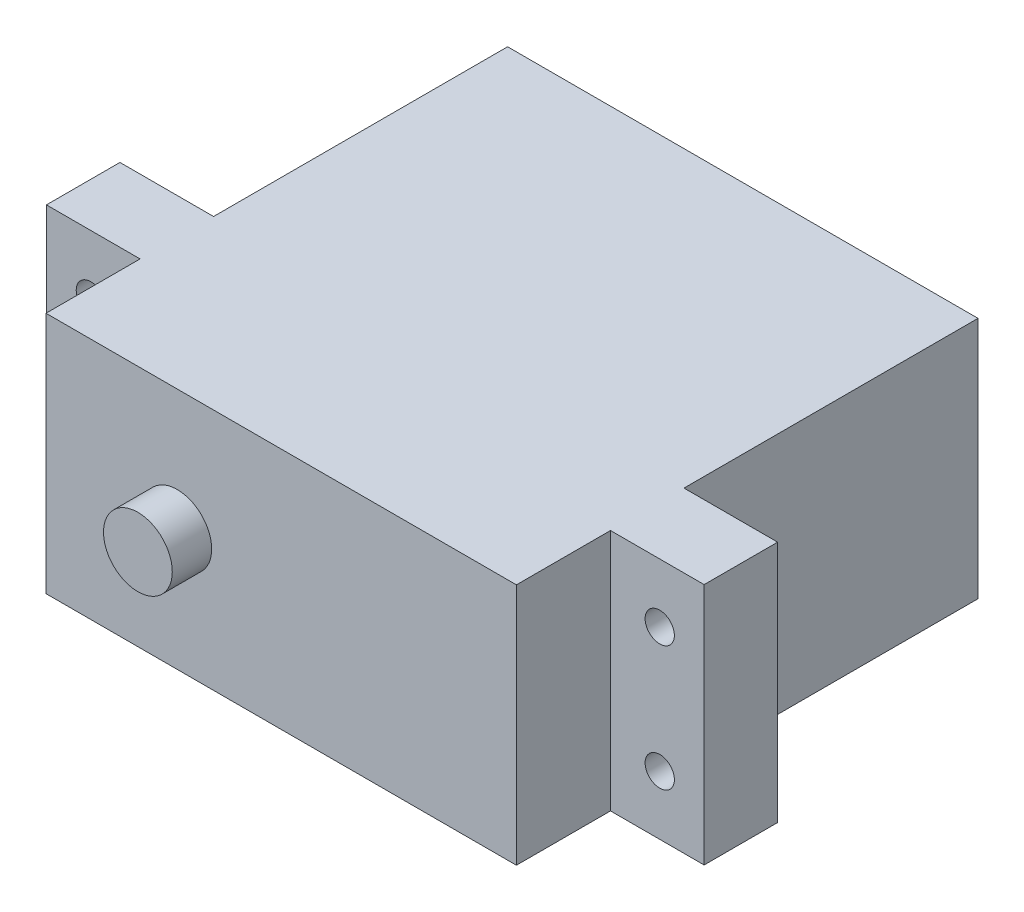
SolidWorks part; units mm, degrees
ref_plane "Front Plane" through (0, 0, 0) normal (0, 0, 1) x (1, 0, 0)
ref_plane "Top Plane" through (0, 0, 0) normal (0, 1, 0) x (1, 0, 0)
ref_plane "Right Plane" through (0, 0, 0) normal (1, 0, 0) x (0, 0, -1)
sketch "Sketch1" plane through (0, 0, 0) normal (0, 0, 1) x (1, 0, 0)
  line L0 (-28.4099, -10.4902) -> (28.4099, -10.4902)
  line L1 (-28.4099, -10.4902) -> (-28.4099, 10.4902)
  line L2 (28.4099, -10.4902) -> (28.4099, 10.4902)
  line L3 (-28.4099, 10.4902) -> (28.4099, 10.4902)
  line L4 (-28.4099, -10.4902) -> (28.4099, 10.4902) construction
  line L5 (28.4099, -10.4902) -> (-28.4099, 10.4902) construction
  point P1 (0, 0)
extrude "Extrude1" add sketch "Sketch1" along normal blind 43.2816
sketch "Sketch3" plane through (0, 0, 43.2816) normal (0, 0, 1) x (1, 0, 0)
  line L0 (-28.4099, 0) -> (-8.9789, 0) construction
  line L1 (-28.4099, 10.4902) -> (-28.4099, -10.4902) construction
  circle A0 centre (-8.9789, 0) radius 2.9718
extrude "Extrude2" cut sketch "Sketch3" against normal blind 3.4036 flip side to cut
sketch "Sketch11" plane through (0, 0, 39.878) normal (0, 0, 1) x (1, 0, 0)
  line L1 (-24.5745, -5.3975) -> (24.5745, -5.3975) construction
  line L2 (-24.5745, -5.3975) -> (-24.5745, 5.3975) construction
  line L3 (-24.5745, 5.3975) -> (24.5745, 5.3975) construction
  line L4 (24.5745, -5.3975) -> (24.5745, 5.3975) construction
  line L5 (-24.5745, -5.3975) -> (24.5745, 5.3975) construction
  line L6 (-24.5745, 5.3975) -> (24.5745, -5.3975) construction
  point P0 (0, 0)
sketch "Sketch8" plane through (0, 0, 0) normal (0, 0, -1) x (-1, 0, 0)
  line L0 (-28.4099, -10.4902) -> (-28.4099, 10.4902)
  line L2 (-28.4099, 10.4902) -> (-20.32, 10.4902)
  line L4 (20.32, -10.4902) -> (20.32, 10.4902)
  line L5 (-28.4099, 10.4902) -> (28.4099, 10.4902) construction
  line L6 (-20.32, 10.4902) -> (-20.32, -10.4902)
  line L7 (28.4099, -10.4902) -> (-28.4099, -10.4902) construction
  line L8 (-20.32, -10.4902) -> (-28.4099, -10.4902)
  line L9 (28.4099, -10.4902) -> (20.32, -10.4902)
  line L10 (20.32, 10.4902) -> (28.4099, 10.4902)
  line L11 (28.4099, 10.4902) -> (28.4099, -10.4902)
  point P10 (23.368, 0)
  point P11 (-23.368, 0)
extrude "Extrude5" cut sketch "Sketch8" against normal blind 25.4
hole_wizard "#39 (0.0995) Diameter Hole1" positions "3DSketch1" profile "Sketch12" hole size "#39" standard "Ansi Inch" end condition through all
sketch3d "3DSketch1"
  point P0 (-24.5745, 5.3975, 39.878)
  point P3 (-24.5745, -5.3975, 39.878)
  point P6 (24.5745, 5.3975, 39.878)
  point P9 (24.5745, -5.3975, 39.878)
sketch "Sketch12" plane through (-24.5745, 5.3975, 39.878) normal (1, 0, 0) x (0, -1, 0)
  line L0 (0, 0) -> (0, 39.878)
  line L1 (0, 39.878) -> (1.2636, 39.878)
  line L2 (1.2636, 39.878) -> (1.2636, 0)
  line L5 (1.2636, 0) -> (0, 0)
  line L11 (0, -6.35) -> (0, 107.95) construction
  dimension "Thru Hole Dia." = 2.5273
  dimension "Thru Hole Depth" = 39.878
sketch "Sketch13" plane through (0, 0, 39.878) normal (0, 0, 1) x (1, 0, 0)
  line L0 (-28.4099, 10.4902) -> (-20.32, 10.4902)
  line L1 (28.4099, 10.4902) -> (-28.4099, 10.4902) construction
  line L2 (-20.32, 10.4902) -> (-20.32, -10.4902)
  line L3 (-28.4099, -10.4902) -> (28.4099, -10.4902) construction
  line L4 (-20.32, -10.4902) -> (-28.4099, -10.4902)
  line L5 (-28.4099, -10.4902) -> (-28.4099, 10.4902)
  line L6 (28.4099, 10.4902) -> (28.4099, -10.4902)
  line L7 (28.4099, -10.4902) -> (20.32, -10.4902)
  line L8 (20.32, -10.4902) -> (20.32, 10.4902)
  line L9 (20.32, 10.4902) -> (28.4099, 10.4902)
extrude "Extrude6" cut sketch "Sketch13" against normal blind 8.128
